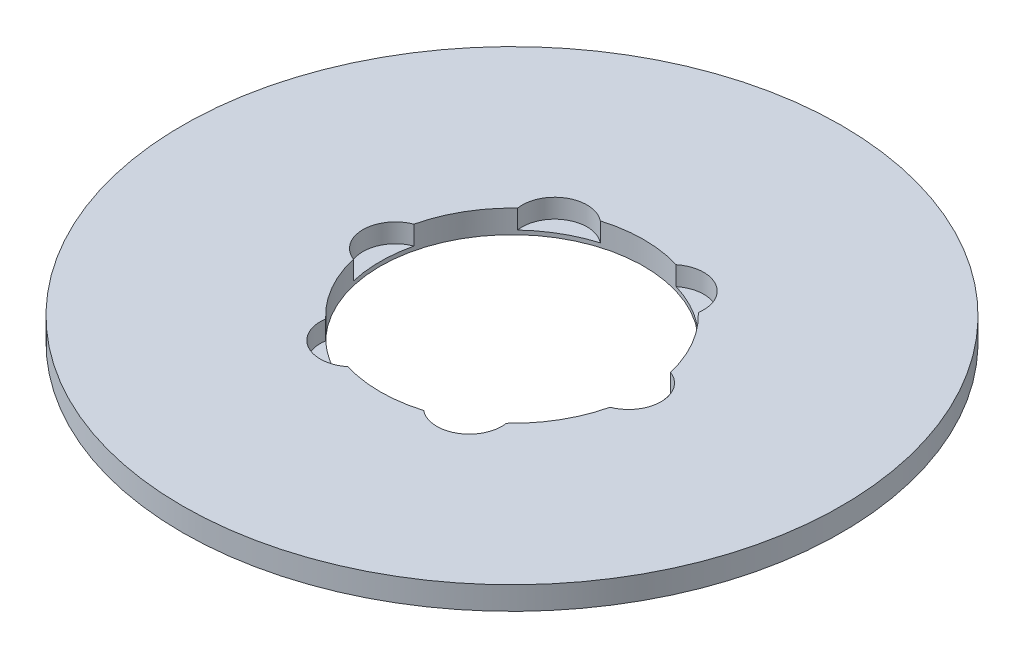
SolidWorks part; units mm, degrees
ref_plane "Front Plane" through (0, 0, 0) normal (0, 0, 1) x (1, 0, 0)
ref_plane "Top Plane" through (0, 0, 0) normal (0, 1, 0) x (1, 0, 0)
ref_plane "Right Plane" through (0, 0, 0) normal (1, 0, 0) x (0, 0, -1)
sketch "Sketch1" plane through (0, 0, 0) normal (0, 1, 0) x (1, 0, 0)
  circle A0 centre (0, 0) radius 100
  dimension "FLANGE_OD" = 200
extrude "Boss-Extrude1" add sketch "Sketch1" along normal blind 7
sketch "Sketch2" plane through (0, 0, 0) normal (0, 1, 0) x (1, 0, 0)
  circle A0 centre (0, 0) radius 40
  dimension "BORE_D" = 80
extrude "Cut-Extrude1" cut sketch "Sketch2" along normal through all
sketch "Sketch3" plane through (0, 7, 0) normal (0, 1, 0) x (1, 0, 0)
  circle A0 centre (0, 0) radius 35.3876 construction
  circle A1 centre (-35.3876, 0) radius 9.8464
  dimension "BOLT_D" = 19.6927
  dimension "BOLT_PCD" = 70.7752
extrude "Cut-Extrude2" cut sketch "Sketch3" against normal blind 5.7645
pattern_circular "CirPattern1" count 6 over 360 about axis through (0, 0, 0) along (0, 1, 0) of "Cut-Extrude2"
